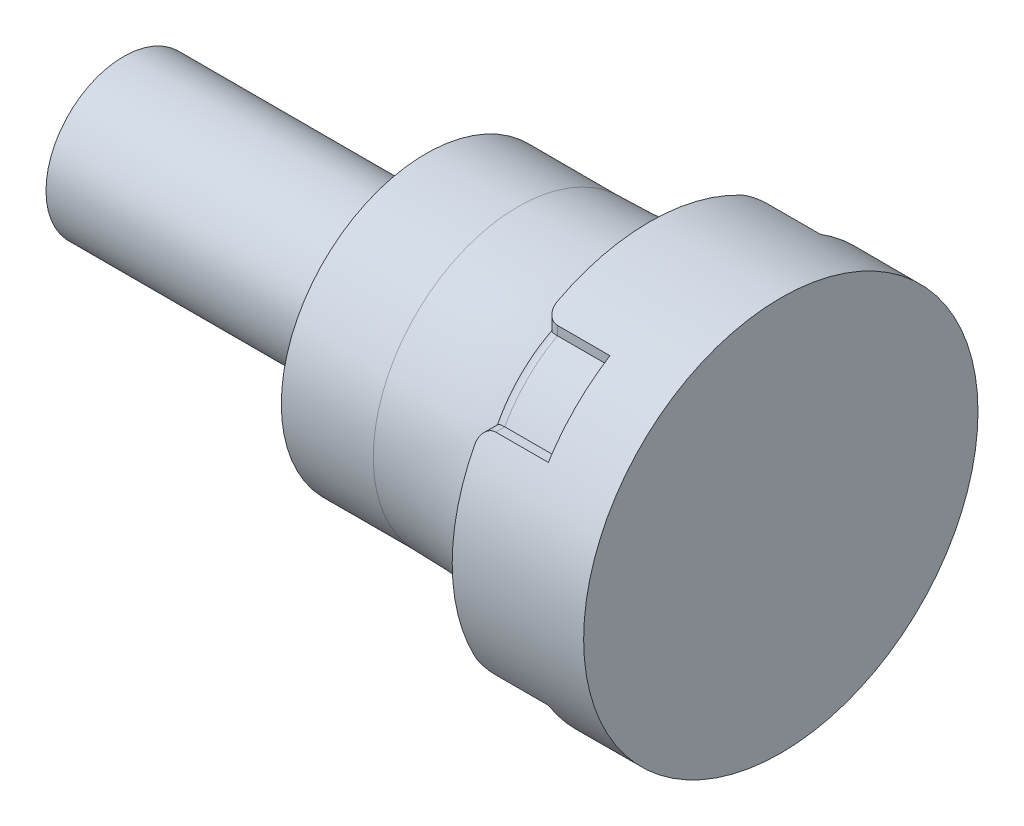
SolidWorks part; units mm, degrees
material "ABS"
ref_plane "Plane1" through (0, 0, 0) normal (0, 0, 1) x (1, 0, 0)
ref_plane "Plane2" through (0, 0, 0) normal (0, 1, 0) x (1, 0, 0)
ref_plane "Plane3" through (0, 0, 0) normal (1, 0, 0) x (0, 0, -1)
sketch "HoldingSke" plane through (0, 0, 0) normal (0, 1, 0) x (1, 0, 0)
  line L0 (0, 0) -> (0.1057, -0.2266)
  line L1 (-15, 0) -> (100, 0) construction
  line L2 (0, 0) -> (-2.1039, 2.3779)
  line L3 (0, 0) -> (-11.863, 4.5341)
  line L4 (0, 0) -> (3.6497, 7.8269)
  line L5 (0, 0) -> (-46.8476, -17.4728)
  line L6 (0, 0) -> (-8.2896, -5.593)
  line L7 (-2.1039, 2.3779) -> (8.6586, 51.2059)
  line L8 (-76.2, 54.61) -> (-74.8, 54.61)
  line L9 (-71.009, 38.7566) -> (-53.1078, 45.2721)
  line L10 (-76.2, 71.12) -> (104.1128, 71.12)
  line L11 (0, 0) -> (-10, 0)
  line L12 (-76.2, 101.6) -> (-76.073, 101.6)
  line L13 (24.9733, 27.94) -> (52.9518, 28.4284)
  line L14 (24.9733, 27.94) -> (24.9743, 27.94)
  line L15 (24.9733, 27.94) -> (100.4006, 29.5858)
  line L16 (-63.627, -4) -> (-12.827, -4)
  circle A0 centre (0, 0) radius 4
  circle A1 centre (0, 0) radius 6
  circle A2 centre (0, 0) radius 6
  circle A3 centre (0, 0) radius 4
  dimension "Num_teeth" = 65
  dimension "Pitch_radius" = 180.3128
  dimension "Width" = 10
  dimension "Thickness" = 10
sketch "BasProSke" plane through (0, 0, 0) normal (0, 1, 0) x (1, 0, 0)
  line L0 (-10, 0) -> (60, 0) construction
  line L1 (0, 0) -> (0, 134)
  line L2 (0, 0) -> (10, 0)
  line L3 (10, 0) -> (10, 134)
  line L4 (10, 134) -> (0, 134)
  dimension "Thickness" = 10
  dimension "Diameter" = 268
revolve "Base-Revolve" add sketch "BasProSke" angle 360 about L0
sketch "TooCutSke" plane through (0, 0, 0) normal (1, 0, 0) x (0, 0, -1)
  line L1 (0, 0) -> (0, 107) construction
  line L2 (0, 0) -> (-3.3635, 129.9565) construction
  line L3 (0, 0) -> (-12.5583, 259.6309) construction
  line L4 (-3.3635, 129.9565) -> (-6.2792, 129.8155) construction
  arc A0 (1.6677, 124.9879) -> (-1.6677, 124.9879) centre (0, 0) ccw
  arc A1 (5.1425, 133.9267) -> (-5.1425, 133.9267) centre (0, 0) ccw
  circle A2 centre (0, 0) radius 130 construction
  circle A3 centre (0, 0) radius 122.16 construction
  arc A4 (-1.6677, 124.9879) -> (-5.1425, 133.9267) centre (-51.6653, 110.6968) ccw
  arc A5 (5.1425, 133.9267) -> (1.6677, 124.9879) centre (51.6653, 110.6968) ccw
extrude "ToothCut" cut sketch "TooCutSke" along normal through all
fillet "Breaks" [suppressed] radius 0.08
fillet "RootFillets" [suppressed] radius 1.001
pattern_circular "TeethCuts" count 65 every 5.538 about axis through (-10, 0, 0) along (1, 0, 0) of "ToothCut", "RootFillets", "Breaks"
sketch "HubNeaOneSke" plane through (0, 0, 0) normal (-1, 0, 0) x (0, 0, 1)
  circle A0 centre (0, 0) radius 6
  dimension "Diameter" = 12
extrude "HubNearOne" add sketch "HubNeaOneSke" along normal blind 40.0001
sketch "HubNeaBotSke" plane through (0, 0, 0) normal (-1, 0, 0) x (0, 0, 1)
  circle A0 centre (0, 0) radius 6
  dimension "Diameter" = 12
extrude "HubNearBoth" [suppressed] add sketch "HubNeaBotSke" along normal blind 20
ref_plane "FarPln" through (10, 0, 0) normal (1, 0, 0) x (0, 0, -1)
sketch "HubFarSke" plane through (10, 0, 0) normal (1, 0, 0) x (0, 0, -1)
  circle A0 centre (0, 0) radius 6
  dimension "Diameter" = 12
extrude "HubFar" [suppressed] add sketch "HubFarSke" along normal blind 20
sketch "BorSke" plane through (0, 0, 0) normal (1, 0, 0) x (0, 0, -1)
  circle A0 centre (0, 0) radius 4
  dimension "Diameter" = 8
extrude "Bore" cut sketch "BorSke" along normal mid plane 100.0001
sketch "KeySke" plane through (0, 0, 0) normal (1, 0, 0) x (0, 0, -1)
  line L0 (-1.5, 0) -> (-1.5, 5.4)
  line L1 (-1.5, 5.4) -> (1.5, 5.4)
  line L2 (1.5, 5.4) -> (1.5, 0)
  line L3 (0, 0) -> (0, 34) construction
  line L4 (-1.5, 0) -> (1.5, 0)
  dimension "Width" = 3
extrude "Keyway" [suppressed] cut sketch "KeySke" along normal mid plane 100.0001
pattern_circular "Keyway2" [suppressed] count 2 every 90 about axis through (-10, 0, 0) along (1, 0, 0)
sketch "Esquisse1" plane through (10, 0, 0) normal (1, 0, 0) x (0, 0, -1)
  line L0 (0, 0) -> (0, 125) construction
  line L1 (100, 3) -> (25, 3)
  line L2 (100, -3) -> (25, -3)
  line L3 (-3, 100) -> (-3, 25)
  line L4 (-3, 25) -> (3, 25)
  line L5 (3, 100) -> (3, 25)
  line L6 (-3, 100) -> (3, 25) construction
  line L7 (-3, 25) -> (3, 100) construction
  line L8 (3, -100) -> (3, -25)
  line L9 (-3, -100) -> (-3, -25)
  line L10 (-100, -3) -> (-25, -3)
  line L11 (-100, 3) -> (-25, 3)
  arc A0 (-3, 25) -> (3, 25) centre (0, 25) ccw
  arc A1 (3, 100) -> (-3, 100) centre (0, 100) ccw
  arc A2 (100, -3) -> (100, 3) centre (100, 0) ccw
  arc A3 (25, 3) -> (25, -3) centre (25, 0) ccw
  arc A4 (-3, -100) -> (3, -100) centre (0, -100) ccw
  arc A5 (3, -25) -> (-3, -25) centre (0, -25) ccw
  arc A6 (-100, 3) -> (-100, -3) centre (-100, 0) ccw
  arc A7 (-25, -3) -> (-25, 3) centre (-25, 0) ccw
  point P3 (0, 62.5)
  point P35 (0, 0)
  dimension "D1" = 25
  dimension "D2" = 75
  dimension "D3" = 6
  dimension "D4" = 4
extrude "Enlèv. mat.-Extru.1" cut sketch "Esquisse1" against normal blind 10 contours L5 A1 L3 L4 | L4 A0 | L1 A3 L2 A2 | L10 A7 L11 A6 | L8 A5 L9 A4
sketch "Esquisse3" plane through (0, 0, 0) normal (-1, 0, 0) x (0, 0, 1)
  line L0 (0, 0) -> (-113, 0) construction
  line L1 (-113, 0) -> (-113, 8) construction
  line L2 (-113, -8) -> (-113, -18)
  line L3 (-113, 8) -> (-12, 8)
  line L4 (-113, 8) -> (-113, 18)
  line L5 (-113, 18) -> (-18, 18)
  line L6 (-12, 8) -> (-12, 12)
  line L7 (-12, -8) -> (-12, -12)
  line L8 (-113, -8) -> (-12, -8)
  line L9 (-113, -18) -> (-18, -18)
  line L10 (8, 113) -> (8, 12)
  line L11 (18, 113) -> (18, 18)
  line L12 (8, 12) -> (12, 12)
  line L13 (8, 113) -> (18, 113)
  line L14 (-8, 113) -> (-8, 12)
  line L15 (-8, 113) -> (-18, 113)
  line L16 (-18, 113) -> (-18, 18)
  line L17 (-8, 12) -> (-12, 12)
  line L18 (113, -8) -> (12, -8)
  line L19 (113, -18) -> (18, -18)
  line L20 (12, -8) -> (12, -12)
  line L21 (113, -8) -> (113, -18)
  line L22 (113, 8) -> (12, 8)
  line L23 (113, 8) -> (113, 18)
  line L24 (113, 18) -> (18, 18)
  line L25 (12, 8) -> (12, 12)
  line L26 (-8, -113) -> (-8, -12)
  line L27 (-18, -113) -> (-18, -18)
  line L28 (-8, -12) -> (-12, -12)
  line L29 (-8, -113) -> (-18, -113)
  line L30 (8, -113) -> (8, -12)
  line L31 (8, -113) -> (18, -113)
  line L32 (18, -113) -> (18, -18)
  line L33 (8, -12) -> (12, -12)
  point P38 (0, 0)
  dimension "D1" = 113
  dimension "D2" = 8
  dimension "D4" = 10
  dimension "D5" = 4
extrude "Enlèv. mat.-Extru.2" cut sketch "Esquisse3" against normal blind 5
fillet "Congé1" radius 10 8 edges at (2.5, -18, -18) (2.5, 18, -18) (2.5, 18, 18) (2.5, -18, 18) (2.5, -12, 12) (2.5, -12, -12) (2.5, 12, 12) (2.5, 12, -12)
fillet "Congé2" radius 2 16 edges at (2.5, 113, -18) (2.5, 113, -8) (2.5, 113, 8) (2.5, 113, 18) (2.5, 18, 113) (2.5, 8, 113) (2.5, -8, 113) (2.5, -18, 113) (2.5, -113, 18) (2.5, -113, 8) (2.5, -113, -8) (2.5, -113, -18) (2.5, -18, -113) (2.5, -8, -113) (2.5, 8, -113) (2.5, 18, -113)
sketch "Esquisse4" plane through (0, 0, 0) normal (-1, 0, 0) x (0, 0, 1)
  line L0 (0, 0) -> (35.3553, 35.3553) construction
  line L1 (35.3553, 35.3553) -> (35.3553, 93.5414)
  line L2 (35.3553, 35.3553) -> (93.5414, 35.3553)
  line L3 (35.3553, -35.3553) -> (93.5414, -35.3553)
  line L4 (35.3553, -35.3553) -> (35.3553, -93.5414)
  line L5 (-35.3553, -35.3553) -> (-35.3553, -93.5414)
  line L6 (-35.3553, -35.3553) -> (-93.5414, -35.3553)
  line L7 (-35.3553, 35.3553) -> (-93.5414, 35.3553)
  line L8 (-35.3553, 35.3553) -> (-35.3553, 93.5414)
  arc A0 (35.3553, 93.5414) -> (93.7151, 34.8925) centre (0, 0) cw
  arc A1 (93.5414, -35.3553) -> (34.8925, -93.7151) centre (0, 0) cw
  arc A2 (-35.3553, -93.5414) -> (-93.7151, -34.8925) centre (0, 0) cw
  arc A3 (-93.5414, 35.3553) -> (-34.8925, 93.7151) centre (0, 0) cw
  point P21 (0, 0)
  dimension "D2" = 4
  dimension "D1" = 50
extrude "Enlèv. mat.-Extru.3" cut sketch "Esquisse4" against normal through all contours A3 L7 L8 | A0 L1 L2 | A1 L3 L4 | A2 L5 L6
fillet "Congé3" radius 10 4 edges at (5, -35.3553, -35.3553) (5, -35.3553, 35.3553) (5, 35.3553, 35.3553) (5, 35.3553, -35.3553)
fillet "Congé4" radius 2 8 edges at (5, -35.3553, -93.5414) (5, -93.5414, -35.3553) (5, -93.5414, 35.3553) (5, -35.3553, 93.5414) (5, 35.3553, 93.5414) (5, 93.5414, 35.3553) (5, 35.3553, -93.5414) (5, 93.5414, -35.3553)
fillet "Congé5" radius 1 48 edges at (0, 8, 61.5) (0, 8.5858, 112.4142) (0, 13, 113) (0, 17.4142, 112.4142) (0, 61.5, 8) (0, 112.4142, 8.5858) (0, 113, 13) (0, 112.4142, 17.4142) (0, 69.5, 18) (0, 20.9289, 20.9289) (0, -61.5, 8) (0, -112.4142, 8.5858) (0, -113, 13) (0, -112.4142, 17.4142) (0, -8, 61.5) (0, -8.5858, 112.4142) (0, -13, 113) (0, -17.4142, 112.4142) (0, -18, 69.5) (0, -20.9289, 20.9289) (0, -61.5, -8) (0, -112.4142, -8.5858) (0, -113, -13) (0, -112.4142, -17.4142) (0, -69.5, -18) (0, -20.9289, -20.9289) (0, -18, -69.5) (0, -17.4142, -112.4142) (0, -13, -113) (0, -8.5858, -112.4142) (0, 61.5, -8) (0, 112.4142, -8.5858) (0, 113, -13) (0, 112.4142, -17.4142) (0, 69.5, -18) (0, 20.9289, -20.9289) (0, 8, -61.5) (0, 8.5858, -112.4142) (0, 13, -113) (0, 17.4142, -112.4142) (0, 10.2887, 10.2887) (0, -10.2887, 10.2887) (0, 18, 69.5) (0, -69.5, 18) (0, -10.2887, -10.2887) (0, -8, -61.5) (0, 10.2887, -10.2887) (0, 18, -69.5)
sketch "Esquisse5" plane through (0, 0, 0) normal (-1, 0, 0) x (0, 0, 1)
  circle A0 centre (0, 0) radius 11
  circle A1 centre (0, 0) radius 6
  dimension "D1" = 22
extrude "Boss.-Extru.1" add sketch "Esquisse5" along normal blind 17
fillet "Congé6" radius 2 1 edges at (0, 0, -11)
sketch "Esquisse6" plane through (-40.0001, 0, 0) normal (-1, 0, 0) x (0, 0, 1)
  line L0 (0, 0) -> (0, 3) construction
  line L1 (-2.6458, 3) -> (2.6458, 3)
  arc A1 (-2.6458, 3) -> (2.6458, 3) centre (0, 0) cw
  point P8 (0, 3)
  circle M2 centre (0, 0) radius 4
  dimension "D1" = 3
extrude "Boss.-Extru.2" add sketch "Esquisse6" against normal blind 30 contours L1 M2
sketch "Esquisse7" plane through (-10.0001, 0, 0) normal (1, 0, 0) x (0, 0, -1)
  circle A0 centre (0, 0) radius 4
extrude "Boss.-Extru.3" add sketch "Esquisse7" along normal up to surface (20.0001 mm away) up to face at (10, -56.8058, 56.8058)
sketch "Esquisse8" plane through (-40.0001, 0, 0) normal (-1, 0, 0) x (0, 0, 1)
  circle A0 centre (0, 0) radius 5.9
  circle A1 centre (0, 0) radius 6
  dimension "D1" = 11.8
  dimension "D2" = 12
extrude "Enlèv. mat.-Extru.4" cut sketch "Esquisse8" against normal blind 23
sketch "Esquisse9" plane through (-10.0001, 0, 0) normal (-1, 0, 0) x (0, 0, 1)
  circle A0 centre (0, 0) radius 15
  circle A1 centre (0, 0) radius 170.6659
  dimension "D1" = 30
extrude "Enlèv. mat.-Extru.8" cut sketch "Esquisse9" against normal through all
equation "' \"Module@HoldingSke\" = 6.35"
equation "' \"Num_teeth@HoldingSke\" = 12"
equation "' \"Ap@HoldingSke\" =  20"
equation "' \"Ap@HoldingSke\" = 20"
equation "' \"Width@HoldingSke\" = 0.5 * 25.4"
equation "' \"Hub_dia@HoldingSke\"= 1 * 25.4"
equation "' \"Hub_dia@HoldingSke\" = 1 * 25.4"
equation "' \"Overall_len@HoldingSke\" = 1.0 * 25.4"
equation "' \"Bore@HoldingSke\" = 0.75 * 25.4"
equation "' \"T_dim@HoldingSke\" = 0.1 * 25.4"
equation "' \"Width@KeySke\" = 0.25 * 25.4"
equation "' \"Show_teeth@HoldingSke\" = 13"
equation "' \"Backlash@HoldingSke\" = 0.009 * 25.4"
equation "' \"Addendum_fac@HoldingSke\" = 1.0"
equation "' \"Dedendum_fac@HoldingSke\" = 1.25"
equation "' \"Dedendum_add@HoldingSke\" = 0.00005 * 25.4"
equation "' \"Clearance_fac@HoldingSke\" = 0.25"
equation "\"Pitch@HoldingSke\" = 1 / \"Module@HoldingSke\""
equation "\"Overcut_dia@TooCutSke\" = (\"Num_teeth@HoldingSke\" + 2 * \"Addendum_fac@HoldingSke\") / \"Pitch@HoldingSke\" + 0.002 * 25.4"
equation "\"Pitch_dia@TooCutSke\" = \"Num_teeth@HoldingSke\" / \"Pitch@HoldingSke\""
equation "\"Base_dia@TooCutSke\" = \"Num_teeth@HoldingSke\" / \"Pitch@HoldingSke\" * cos((\"Ap@HoldingSke\"  * 3.14159265 / 180))"
equation "\"Root_dia@TooCutSke\" = (\"Num_teeth@HoldingSke\" + 2) / \"Pitch@HoldingSke\" - 2 * (\"Addendum_fac@HoldingSke\" + \"Dedendum_fac@HoldingSke\") / \"Pitch@HoldingSke\" - \"Dedendum_add@HoldingSke\" * 2"
equation "\"Half_ang@TooCutSke\" = 180 / \"Num_teeth@HoldingSke\""
equation "\"Half_CT@TooCutSke\" = \"Num_teeth@HoldingSke\" / \"Pitch@HoldingSke\" * sin((3.14159265 / 2 / \"Num_teeth@HoldingSke\")) / 2 - 7 * \"Backlash@HoldingSke\" / 4"
equation "\"Flank_rad@TooCutSke\" = \"Num_teeth@HoldingSke\" / \"Pitch@HoldingSke\" / 5"
equation "\"Radius@RootFillets\" = \"Clearance_fac@HoldingSke\" / \"Pitch@HoldingSke\" + \"Dedendum_add@HoldingSke\""
equation "\"Break_rad@Breaks\" = 0.02 / \"Pitch@HoldingSke\""
equation "\"Thickness@HoldingSke\" = \"Width@HoldingSke\""
equation "\"OAL@HoldingSke\" = \"Thickness@HoldingSke\""
equation "\"MHD@HoldingSke\" = (\"Num_teeth@HoldingSke\" + 2) / \"Pitch@HoldingSke\" - 2 * (\"Addendum_fac@HoldingSke\" + \"Dedendum_fac@HoldingSke\")  / \"Pitch@HoldingSke\" - \"Dedendum_add@HoldingSke\" * 2"
equation "\"MBD@HoldingSke\" = (\"Num_teeth@HoldingSke\" + 2) / \"Pitch@HoldingSke\" - 2 * (\"Addendum_fac@HoldingSke\" + \"Dedendum_fac@HoldingSke\")  / \"Pitch@HoldingSke\" - \"Dedendum_add@HoldingSke\" * 2 - 0.002 * 25.4"
equation "\"MHD@HoldingSke\" = ((sgn( \"MHD@HoldingSke\" - \"Hub_dia@HoldingSke\" )-1)*( \"MHD@HoldingSke\" - \"Hub_dia@HoldingSke\" ))/-2+ \"Hub_dia@HoldingSke\""
equation "\"MBD@HoldingSke\" = ((sgn( \"MBD@HoldingSke\" - \"Bore@HoldingSke\" )-1)*( \"MBD@HoldingSke\" - \"Bore@HoldingSke\" ))/-2+ \"Bore@HoldingSke\""
equation "\"OAL@HoldingSke\" = ((sgn( \"OAL@HoldingSke\" - \"Overall_len@HoldingSke\" )+1)*( \"OAL@HoldingSke\" - \"Overall_len@HoldingSke\" ))/2 + \"Overall_len@HoldingSke\" + 0.000002 * 25.4"
equation "\"Num_teeth@TeethCuts\" = int( \"Show_teeth@HoldingSke\" ) + 1"
equation "\"Num_teeth@TeethCuts\" = ((sgn( \"Num_teeth@TeethCuts\" - \"Num_teeth@HoldingSke\" )-1)*( \"Num_teeth@TeethCuts\" - \"Num_teeth@HoldingSke\" ))/-2+ \"Num_teeth@HoldingSke\""
equation "\"Num_teeth@TeethCuts\" = ((sgn( \"Num_teeth@TeethCuts\" - 2.0)+1)*( \"Num_teeth@TeethCuts\" - 2.0))/2 +2.0"
equation "\"Angle@TeethCuts\" = 360.0 / \"Num_teeth@HoldingSke\""
equation "\"Diameter@BasProSke\" = (\"Num_teeth@HoldingSke\" + 2 * \"Addendum_fac@HoldingSke\") / \"Pitch@HoldingSke\""
equation "\"Thickness@BasProSke\"  = \"Thickness@HoldingSke\""
equation "' \"Fillet_rad@BasProSke\" =  \"Thickness@HoldingSke\" * 0.05"
equation "' \"Fillet_rad@BasProSke\" = \"Thickness@HoldingSke\" * 0.05"
equation "\"MHD@HoldingSke\" = ((sgn( \"MHD@HoldingSke\" - \"Root_dia@TooCutSke\" )-1)*( \"MHD@HoldingSke\" - \"Root_dia@TooCutSke\" ))/-2+ \"Root_dia@TooCutSke\""
equation "\"Diameter@HubNeaOneSke\" = \"MHD@HoldingSke\""
equation "\"Length@HubNearOne\" = \"OAL@HoldingSke\" - \"Thickness@BasProSke\""
equation "\"Diameter@HubNeaBotSke\" = \"MHD@HoldingSke\""
equation "\"Length@HubNearBoth\" = ( \"OAL@HoldingSke\" - \"Thickness@BasProSke\" ) / 2.0"
equation "\"Thickness@FarPln\" = \"Thickness@BasProSke\""
equation "\"Diameter@HubFarSke\" = \"MHD@HoldingSke\""
equation "\"Length@HubFar\" = ( \"OAL@HoldingSke\" - \"Thickness@BasProSke\" ) / 2.0"
equation "\"Diameter@BorSke\" = \"MBD@HoldingSke\""
equation "\"D1@Bore\" = \"OAL@HoldingSke\" * 2.0"
equation "\"D1@Keyway\" = \"OAL@HoldingSke\" * 2.0"
equation "\"Offset@KeySke\" = \"T_dim@HoldingSke\" + \"MBD@HoldingSke\" / 2.0"
